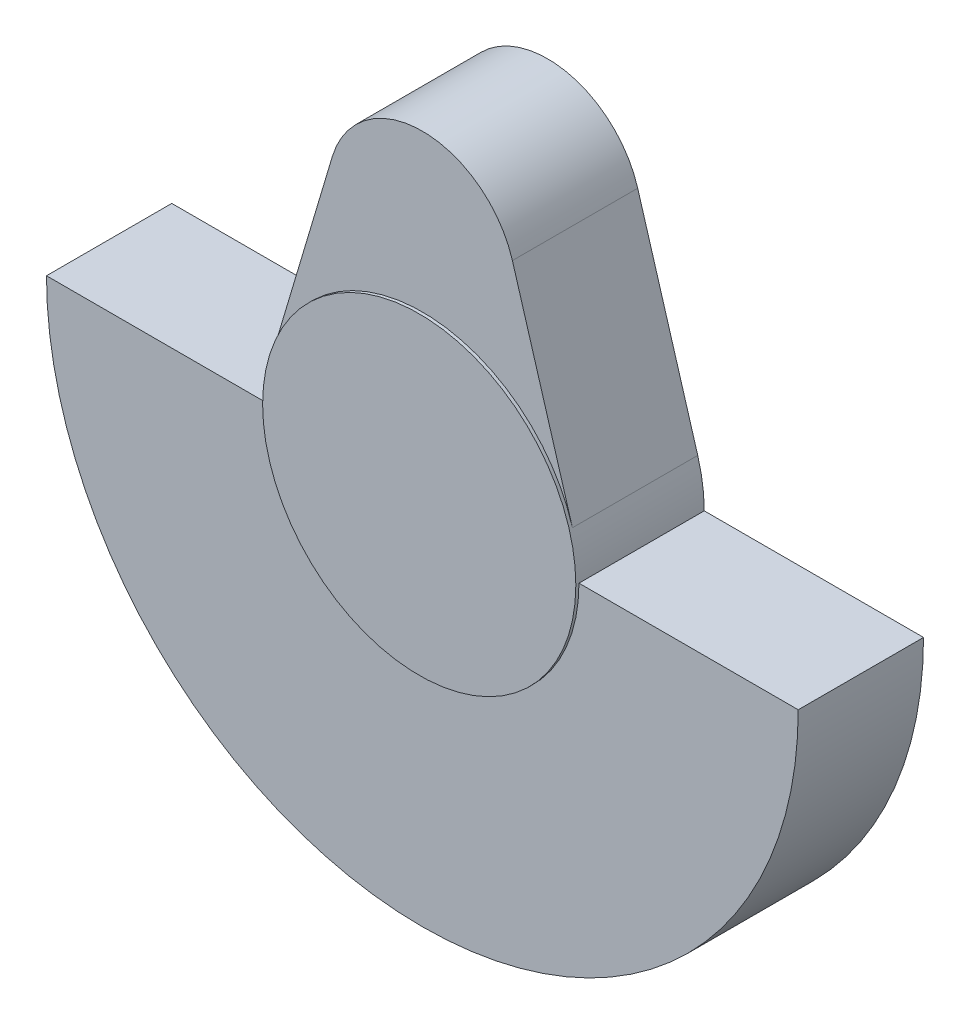
SolidWorks part; units mm, degrees
ref_plane "Front Plane" through (0, 0, 0) normal (0, 0, 1) x (1, 0, 0)
ref_plane "Top Plane" through (0, 0, 0) normal (0, 1, 0) x (1, 0, 0)
ref_plane "Right Plane" through (0, 0, 0) normal (1, 0, 0) x (0, 0, -1)
sketch "Sketch1" plane through (0, 0, 0) normal (0, 0, 1) x (1, 0, 0)
  line L0 (0, 0) -> (0, 70) construction
  line L1 (-28.7494, 78.5714) -> (-47.9157, 14.2857)
  line L2 (28.7494, 78.5714) -> (47.9157, 14.2857)
  line L3 (-41.7399, 35) -> (41.7399, 35) construction
  line L4 (-120, 0) -> (-50, 0)
  line L5 (120, 0) -> (50, 0)
  circle A0 centre (0, 0) radius 50
  arc A1 (-28.7494, 78.5714) -> (28.7494, 78.5714) centre (0, 70) cw
  arc A2 (120, 0) -> (-120, 0) centre (0, 0) cw
  point P10 (0, 35)
  dimension "D1" = 100
  dimension "D2" = 30
  dimension "D4" = 120
  dimension "D3" = 70
extrude "Boss-Extrude1" add sketch "Sketch1" along normal blind 1 and the other way blind 40 contours A0 region at (0, 0, 0)
extrude "Boss-Extrude2" add sketch "Sketch1<3>" against normal up to surface (40 mm away) contours A2 L5 A0 L4 | A1 L1 A0 L2 region at (0, 66.8029, 0) region at (0, -57.171, 0) up to face at (50, 0, -40)
sketch "Sketch1<3>" plane through (0, 0, 0) normal (0, 0, 1) x (1, 0, 0) same geometry as "Sketch1"
equation "\"D2@Sketch1\"=\"D1@Sketch1\"*.3"
equation "\"D3@Sketch1\"=\"D1@Sketch1\"*.7"
equation "\"D4@Sketch1\"=\"D1@Sketch1\"*1.2"
equation "\"D1@Boss-Extrude1\"=\"D1@Sketch1\"*.01"
equation "\"D2@Boss-Extrude1\"=\"D1@Sketch1\"*.4"
